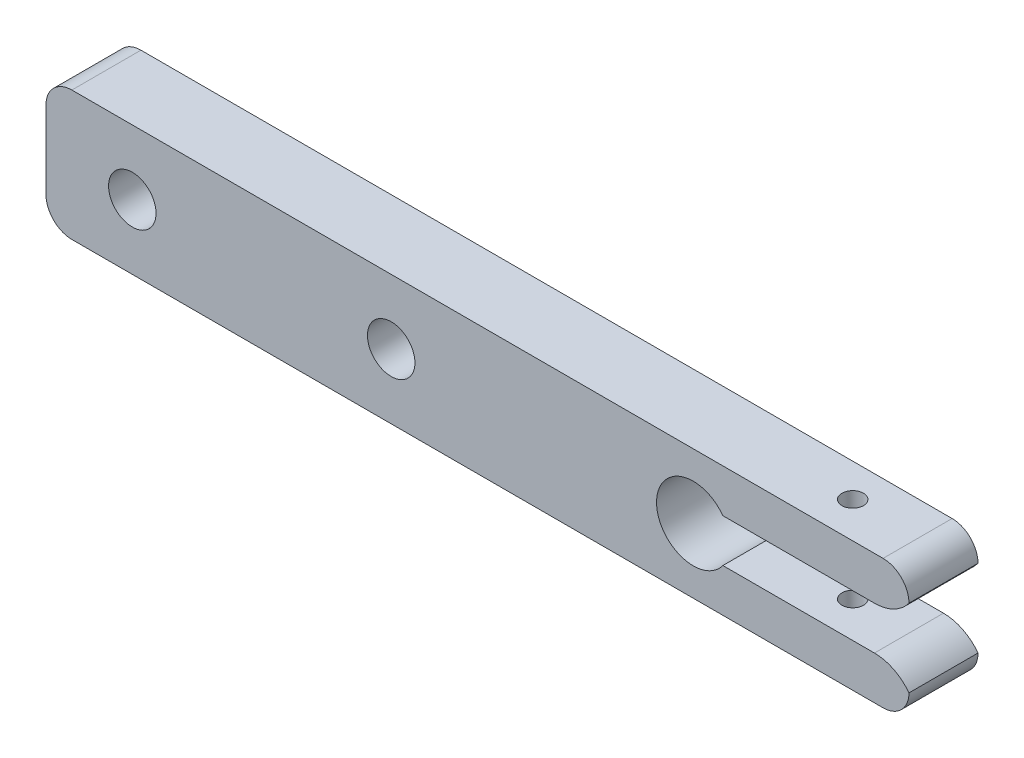
SolidWorks part; units mm, degrees
material "ABS"
ref_plane "Ebene vorne" through (0, 0, 0) normal (0, 0, 1) x (1, 0, 0)
ref_plane "Ebene oben" through (0, 0, 0) normal (0, 1, 0) x (1, 0, 0)
ref_plane "Ebene rechts" through (0, 0, 0) normal (1, 0, 0) x (0, 0, -1)
sketch "Skizze1" plane through (0, 0, 0) normal (0, 0, 1) x (1, 0, 0)
  line L1 (50, 7.5) -> (-50, 7.5)
  line L2 (50, 7.5) -> (50, -7.5)
  line L3 (50, -7.5) -> (-50, -7.5)
  line L4 (-50, 7.5) -> (-50, -7.5)
  line L5 (50, 7.5) -> (-50, -7.5) construction
  line L6 (50, -7.5) -> (-50, 7.5) construction
  line L7 (-50, 0) -> (-40, 0) construction
  line L9 (-40, 0) -> (-10, 0) construction
  circle A0 centre (-10, 0) radius 2.75
  circle A1 centre (-40, 0) radius 2.75
  circle A2 centre (25, 0) radius 4.25
  point P0 (0, 0)
  point P13 (-40, 0)
  dimension "D2" = 5.5
  dimension "D3" = 30
  dimension "D5" = 8.5
  dimension "D7" = 25
  dimension "D1" = 10
  dimension "D4" = 15
  dimension "D6" = 100
extrude "Aufsatz-Linear austragen1" add sketch "Skizze1" along normal blind 8
fillet "Verrundung1" radius 3 4 edges at (-50, -7.5, 4) (50, -7.5, 4) (50, 7.5, 4) (-50, 7.5, 4)
sketch "Skizze2" plane through (0, 0, 8) normal (0, 0, 1) x (1, 0, 0)
  line L0 (25, 0) -> (52.7317, 0) construction
  line L1 (25, 2.5) -> (52.7317, 2.5)
  line L2 (25, -2.5) -> (52.7317, -2.5)
  arc A0 (25, 2.5) -> (25, -2.5) centre (25, 0) ccw
  arc A1 (52.7317, -2.5) -> (52.7317, 2.5) centre (52.7317, 0) ccw
  point P4 (38.8658, 0)
  dimension "D1" = 5
extrude "Schnitt-Linear austragen1" cut sketch "Skizze2" against normal blind 30
hole_wizard "M3 Gewindebohrung1" positions "Skizze4" profile "Skizze3" tap size "M3" standard "DIN" end condition through all
sketch "Skizze4" plane through (0, -7.5, 0) normal (0, -1, 0) x (1, 0, 0)
  point P0 (39.3248, 3.8456)
sketch "Skizze3" plane through (39.3248, -7.5, 3.8456) normal (1, 0, 0) x (0, 0, -1)
  line L0 (0, 0) -> (0, 15)
  line L1 (0, 15) -> (1.25, 15)
  line L2 (1.25, 15) -> (1.25, 0)
  line L5 (1.25, 0) -> (0, 0)
  line L11 (0, -6.35) -> (0, 107.95) construction
  dimension "Bohrerdurchmesser" = 2.5
  dimension "Bohrungstiefe" = 15
cosmetic thread "Bohrungsgewinde1" parameters "D2"=3
fillet "Verrundung2" radius 5 2 edges at (50, -2.5, 4) (50, 2.5, 4)
